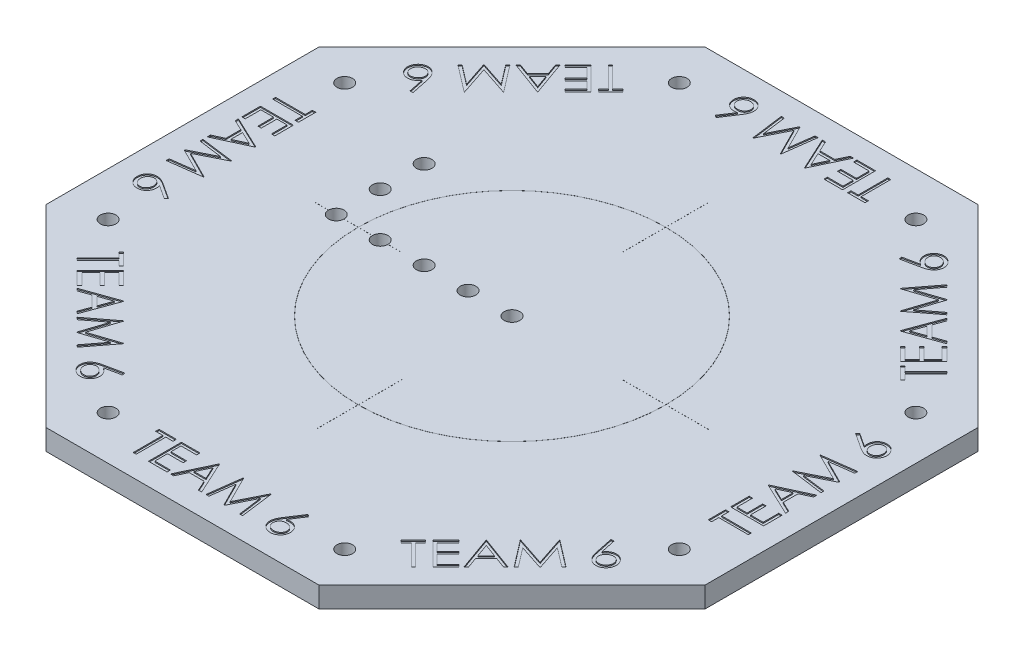
SolidWorks part; units mm, degrees
material "Custom Plastic"
ref_plane "Front Plane" through (0, 0, 0) normal (0, 0, 1) x (1, 0, 0)
ref_plane "Top Plane" through (0, 0, 0) normal (0, 1, 0) x (1, 0, 0)
ref_plane "Right Plane" through (0, 0, 0) normal (1, 0, 0) x (0, 0, -1)
ref_axis "Axis1" through (0, 6.2941, 0) along (0, -1, 0)
sketch "Sketch1" plane through (0, 0, 0) normal (0, 1, 0) x (1, 0, 0)
  line L1 (-39.4538, 95.25) -> (-95.25, 39.4538)
  line L2 (-95.25, 39.4538) -> (-95.25, -39.4538)
  line L3 (-95.25, -39.4538) -> (-39.4538, -95.25)
  line L4 (-39.4538, -95.25) -> (39.4538, -95.25)
  line L5 (39.4538, -95.25) -> (95.25, -39.4538)
  line L6 (95.25, -39.4538) -> (95.25, 39.4538)
  line L7 (95.25, 39.4538) -> (39.4538, 95.25)
  line L8 (39.4538, 95.25) -> (-39.4538, 95.25)
  circle A0 centre (0, 0) radius 95.25 construction
  dimension "D1" = 190.5
extrude "Base" add sketch "Sketch1" along normal blind 5.9944
sketch "Sketch2" plane through (0, 5.9944, 0) normal (0, 1, 0) x (1, 0, 0)
  line L0 (39.4538, 95.25) -> (-39.4538, 95.25) construction
  line L1 (34.1933, 82.55) -> (-34.1933, 82.55)
  line L2 (-34.1933, 82.55) -> (-82.55, 34.1933)
  line L3 (-82.55, 34.1933) -> (-82.55, -34.1933)
  line L4 (-82.55, -34.1933) -> (-34.1933, -82.55)
  line L5 (-34.1933, -82.55) -> (34.1933, -82.55)
  line L6 (34.1933, -82.55) -> (82.55, -34.1933)
  line L7 (82.55, -34.1933) -> (82.55, 34.1933)
  line L8 (82.55, 34.1933) -> (34.1933, 82.55)
  circle A0 centre (0, 0) radius 82.55 construction
  dimension "D1" = 12.7
hole_wizard "Mounting holes" positions "Sketch4" profile "Sketch3" hole size "#8" standard "ANSI Inch"
sketch "Sketch4" plane through (0, 5.9944, 0) normal (0, 1, 0) x (1, 0, 0)
  point P0 (-34.1933, 82.55)
  point P8 (34.1933, 82.55)
  point P11 (82.55, 34.1933)
  point P14 (82.55, -34.1933)
  point P17 (34.1933, -82.55)
  point P20 (-34.1933, -82.55)
  point P23 (-82.55, -34.1933)
  point P26 (-82.55, 34.1933)
sketch "Sketch3" plane through (-34.1933, 5.9944, -82.55) normal (1, 0, 0) x (0, 0, 1)
  line L0 (0, 0) -> (0, 5.9944)
  line L1 (0, 5.9944) -> (2.2479, 5.9944)
  line L2 (2.2479, 5.9944) -> (2.2479, 0)
  line L5 (2.2479, 0) -> (0, 0)
  line L10 (0, 5.9944) -> (-2.2479, 5.9944) construction
  line L11 (0, -6.35) -> (0, 107.95) construction
  dimension "Hole Dia." = 4.4958
  dimension "Hole Depth" = 5.9944
  dimension "Drill Angle" = 180
sketch "Sketch5" plane through (0, 5.9944, 0) normal (0, 1, 0) x (1, 0, 0)
  line L0 (0, 0) -> (-95.25, 0) construction
  line L1 (-95.25, 39.4538) -> (-95.25, -39.4538) construction
  line L2 (-50.8, 0) -> (-50.8, 25.4) construction
  point P4 (-12.7, 0)
  point P5 (-25.4, 0)
  point P7 (-38.1, 0)
  point P8 (-50.8, 0)
  point P11 (-50.8, 12.7)
  dimension "D1" = 12.7
  dimension "D2" = 12.7
  dimension "D3" = 12.7
  dimension "D4" = 12.7
  dimension "D5" = 25.4
hole_wizard "#8 Clearance Hole1" positions "Sketch7" profile "Sketch6" hole size "#8" standard "ANSI Inch" end condition through all
sketch "Sketch7" plane through (0, 5.9944, 0) normal (0, 1, 0) x (1, 0, 0)
  point P0 (0, 0)
  point P3 (-12.7, 0)
  point P6 (-25.4, 0)
  point P9 (-38.1, 0)
  point P12 (-50.8, 0)
  point P15 (-50.8, 12.7)
  point P18 (-50.8, 25.4)
sketch "Sketch6" plane through (0, 5.9944, 0) normal (1, 0, 0) x (0, 0, 1)
  line L0 (0, 0) -> (0, 5.9944)
  line L1 (0, 5.9944) -> (2.2479, 5.9944)
  line L2 (2.2479, 5.9944) -> (2.2479, 0)
  line L5 (2.2479, 0) -> (0, 0)
  line L11 (0, -6.35) -> (0, 107.95) construction
  dimension "Thru Hole Dia." = 4.4958
  dimension "Thru Hole Depth" = 5.9944
sketch "Sketch8" plane through (0, 5.9944, 0) normal (0, 1, 0) x (1, 0, 0)
  line L0 (-39.4538, -95.25) -> (39.4538, -95.25) construction
  line L2 (-45.8038, -88.9) -> (45.8038, -88.9) construction
  line L3 (-95.25, -39.4538) -> (-39.4538, -95.25) construction
  line L4 (39.4538, -95.25) -> (95.25, -39.4538) construction
  text T0 "TEAM 6" font "Century Gothic" height 9.525
  dimension "D1" = 6.35
extrude "Cut-Extrude1" cut sketch "Sketch8" against normal blind 0.3175
pattern_circular "CirPattern1" count 8 over 360 about axis through (0, 6.2941, 0) along (0, -1, 0) of "Cut-Extrude1"
sketch "Sketch9" plane through (0, 5.9944, 0) normal (0, 1, 0) x (1, 0, 0)
  line L0 (0, 57.15) -> (0, 31.75)
  line L1 (57.15, 0) -> (31.75, 0)
  line L2 (0, -57.15) -> (0, -31.75)
  line L3 (-57.15, 0) -> (-31.75, 0)
  circle A0 centre (0, 0) radius 44.45
  point P5 (0, 44.45)
  point P6 (44.45, 0)
  point P7 (0, -44.45)
  point P8 (-44.45, 0)
  point P15 (-5.4202, -4.3363)
  dimension "D1" = 88.9
  dimension "D2" = 25.4
extrude "Cut-Extrude-Thin2" cut sketch "Sketch9" against normal blind 0.3175 thin thin type one direction wall 0.0254
equation "\"MAT_THICKNESS\"=0.236"
equation "\"D1@Base\"=\"MAT_THICKNESS\""
